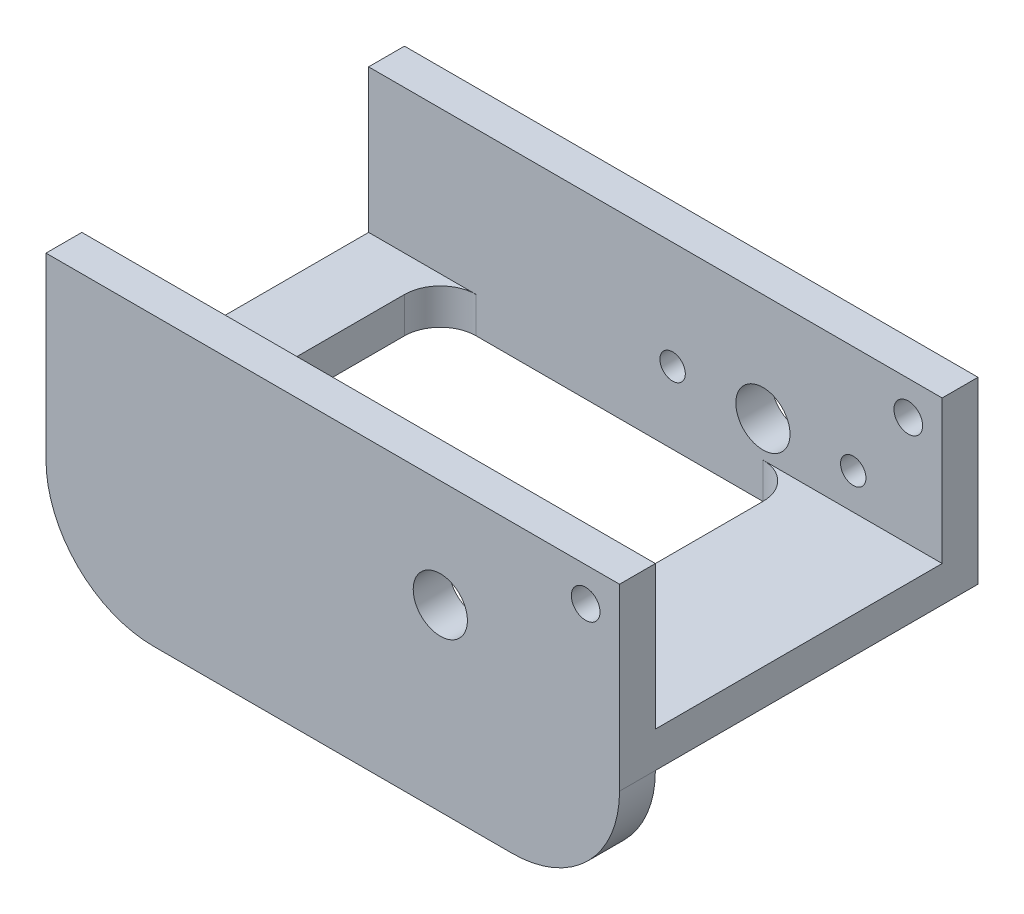
SolidWorks part; units mm, degrees
ref_plane "Front Plane" through (0, 0, 0) normal (0, 0, 1) x (1, 0, 0)
ref_plane "Top Plane" through (0, 0, 0) normal (0, 1, 0) x (1, 0, 0)
ref_plane "Right Plane" through (0, 0, 0) normal (1, 0, 0) x (0, 0, -1)
sketch "Sketch1" plane through (0, 0, 0) normal (0, 1, 0) x (1, 0, 0)
  line L1 (0, 0) -> (101.6, 0)
  line L2 (0, 0) -> (0, 63.5)
  line L3 (0, 63.5) -> (101.6, 63.5)
  line L4 (101.6, 0) -> (101.6, 63.5)
  dimension "D1" = 63.5
  dimension "D2" = 101.6
extrude "Boss-Extrude1" add sketch "Sketch1" along normal blind 50.8
sketch "Sketch2" plane through (101.6, 0, 0) normal (1, 0, 0) x (0, 0, -1)
  line L0 (63.5, 50.8) -> (63.5, 0) construction
  line L1 (57.15, 50.8) -> (6.35, 50.8)
  line L2 (57.15, 50.8) -> (57.15, 25.4)
  line L3 (57.15, 25.4) -> (6.35, 25.4)
  line L4 (6.35, 50.8) -> (6.35, 25.4)
  line L5 (63.5, 0) -> (6.35, 0)
  line L6 (63.5, 0) -> (63.5, 19.05)
  line L7 (63.5, 19.05) -> (6.35, 19.05)
  line L8 (6.35, 0) -> (6.35, 19.05)
  line L9 (0, 50.8) -> (0, 0) construction
  point P10 (0, 0)
  point P15 (57.15, 26.6445)
  dimension "D1" = 19.05
  dimension "D2" = 6.35
  dimension "D3" = 6.35
  dimension "D4" = 6.35
extrude "Cut-Extrude1" cut sketch "Sketch2" against normal up to next
sketch "Sketch5" plane through (0, 25.4, 0) normal (0, 1, 0) x (1, 0, 0)
  line L0 (0, 6.35) -> (101.6, 6.35) construction
  line L1 (12.7, 6.35) -> (76.2, 6.35)
  line L2 (12.7, 6.35) -> (12.7, 57.15)
  line L3 (12.7, 57.15) -> (76.2, 57.15)
  line L4 (76.2, 6.35) -> (76.2, 57.15)
  line L5 (0, 57.15) -> (101.6, 57.15) construction
  line L6 (0, 57.15) -> (0, 6.35) construction
  line L7 (101.6, 6.35) -> (101.6, 57.15) construction
  dimension "D1" = 12.7
  dimension "D2" = 25.4
extrude "Cut-Extrude5" cut sketch "Sketch5" against normal up to surface (6.35 mm away) up to face at (50.8, 19.05, -34.925)
sketch "Sketch3" plane through (0, 0, -63.5) normal (0, 0, -1) x (-1, 0, 0)
  line L0 (-85.85, 31.75) -> (-53.85, 31.75) construction
  line L1 (-101.6, 50.8) -> (-101.6, 19.05) construction
  line L2 (0, 19.05) -> (-101.6, 19.05) construction
  circle A0 centre (-85.85, 31.75) radius 2.25
  circle A1 centre (-69.85, 31.75) radius 4.8
  circle A2 centre (-53.85, 31.75) radius 2.25
  point P6 (0, 0)
  point P7 (0, 0)
  point P12 (-53.85, 36.5528)
  dimension "D2" = 4.5
  dimension "D6" = 9.6
  dimension "D1" = 32
  dimension "D3" = 31.75
  dimension "D4" = 12.7
  dimension "D5" = 32
extrude "Cut-Extrude2" cut sketch "Sketch3" against normal up to next contours A0 | A2 region at (85.85, 31.75, -63.5) region at (53.85, 31.75, -63.5)
extrude "Cut-Extrude3" cut sketch "Sketch3<4>" against normal up to surface (63.5 mm away) contours A1 L0 | L0 A1 region at (69.85, 33.7872, -63.5) region at (69.85, 29.7128, -63.5) up to face at (50.8, 25.4, 0)
sketch "Sketch3<4>" plane through (0, 0, -63.5) normal (0, 0, -1) x (-1, 0, 0) same geometry as "Sketch3"
sketch "Sketch4" plane through (0, 0, -63.5) normal (0, 0, -1) x (-1, 0, 0)
  line L0 (-101.6, 50.8) -> (-101.6, 19.05) construction
  line L1 (-101.6, 50.8) -> (0, 50.8) construction
  circle A0 centre (-95.6, 44.8) radius 2.54
  point P2 (0, 0)
  dimension "D3" = 5.08
  dimension "D1" = 6
  dimension "D2" = 6
extrude "Cut-Extrude4" cut sketch "Sketch4" against normal up to surface (63.5 mm away) up to face at (65.05, 31.75, 0)
fillet "Fillet1" radius 19.05 2 edges at (0, 0, -3.175) (101.6, 0, -3.175)
fillet "Fillet2" radius 6.35 4 edges at (76.2, 22.225, -6.35) (76.2, 22.225, -57.15) (12.7, 22.225, -57.15) (12.7, 22.225, -6.35)
